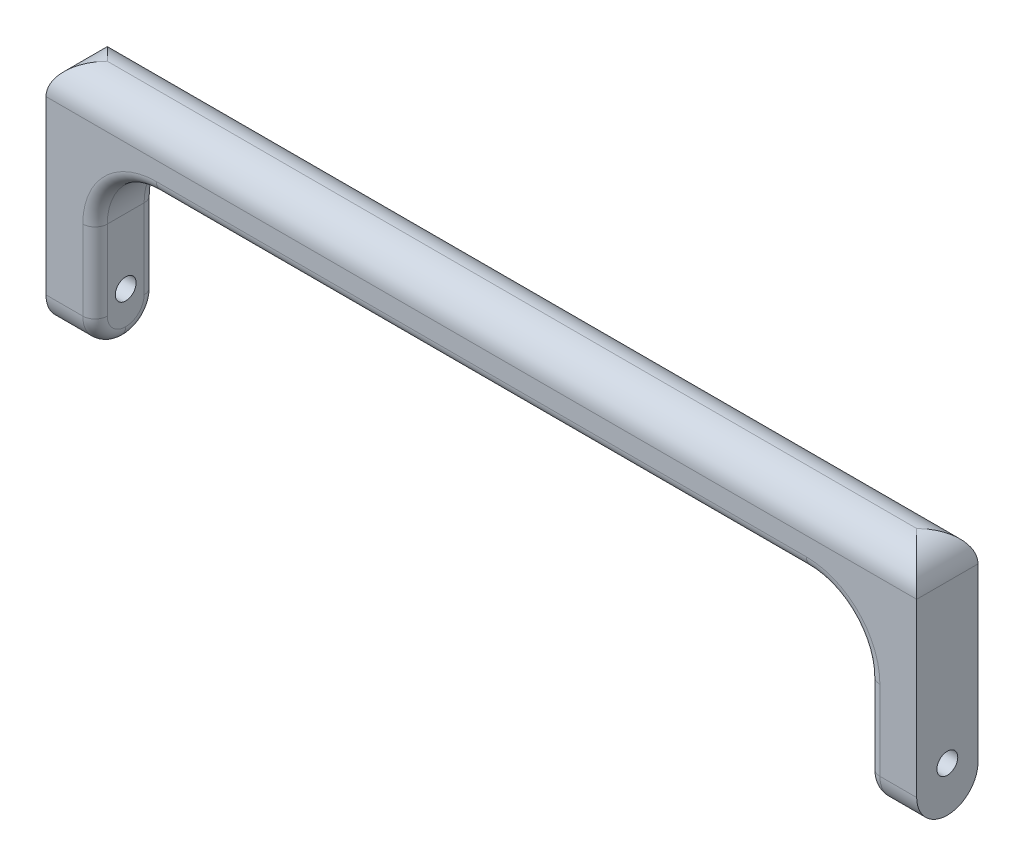
SolidWorks part; units mm, degrees
ref_plane "Front Plane" through (0, 0, 0) normal (0, 0, 1) x (1, 0, 0)
ref_plane "Top Plane" through (0, 0, 0) normal (0, 1, 0) x (1, 0, 0)
ref_plane "Right Plane" through (0, 0, 0) normal (1, 0, 0) x (0, 0, -1)
sketch "Sketch1" plane through (0, 0, 0) normal (0, 0, 1) x (1, 0, 0)
  line L0 (0, 0) -> (0, -50.4722) construction
  line L1 (-53, 0) -> (53, 0)
  line L2 (63, -10) -> (63, -28)
  line L3 (63, -28) -> (71, -28)
  line L4 (71, -28) -> (71, 0)
  line L5 (71, 0) -> (71, 10)
  line L6 (71, 10) -> (-71, 10)
  line L7 (0, 10) -> (0, 0)
  line L8 (-71, 0) -> (-71, 10)
  line L9 (-71, -28) -> (-71, 0)
  line L10 (-63, -28) -> (-71, -28)
  line L11 (-63, -10) -> (-63, -28)
  arc A0 (53, 0) -> (63, -10) centre (53, -10) cw
  arc A1 (-53, 0) -> (-63, -10) centre (-53, -10) ccw
  point P7 (63, 0)
  point P12 (63, 0)
  point P20 (-63, 0)
  dimension "D3" = 8
  dimension "D5" = 10
  dimension "D1" = 63
  dimension "D2" = 28
  dimension "D4" = 10
extrude "Boss-Extrude1" add sketch "Sketch1" along normal mid plane 10 contours A1 L1 L7 L6 L8 L9 L10 L11 | L1 A0 L2 L3 L4 L5 L6 L7 region at (-43.4524, 0.3831, 0) region at (43.4524, 0.3831, 0)
fillet "Fillet1" radius 5 4 edges at (-67, -28, -5) (-67, -28, 5) (67, -28, -5) (67, -28, 5)
fillet "Fillet2" radius 5 4 edges at (0, 10, 5) (0, 10, -5) (71, 10, 0) (-71, 10, 0)
fillet "Fillet3" radius 2 14 edges at (-60.0711, -2.9289, -5) (-63, -16.5, -5) (-63, -26.5355, -3.5355) (-63, -26.5355, 3.5355) (-63, -16.5, 5) (-60.0711, -2.9289, 5) (0, 0, 5) (60.0711, -2.9289, 5) (63, -16.5, 5) (63, -26.5355, 3.5355) (63, -26.5355, -3.5355) (63, -16.5, -5) (60.0711, -2.9289, -5) (0, 0, -5)
sketch "Sketch2" plane through (71, 0, 0) normal (1, 0, 0) x (0, 0, -1)
  circle A0 centre (0, -20.6526) radius 1.7
  dimension "D1" = 3.4
extrude "Cut-Extrude1" cut sketch "Sketch2" against normal blind 147
